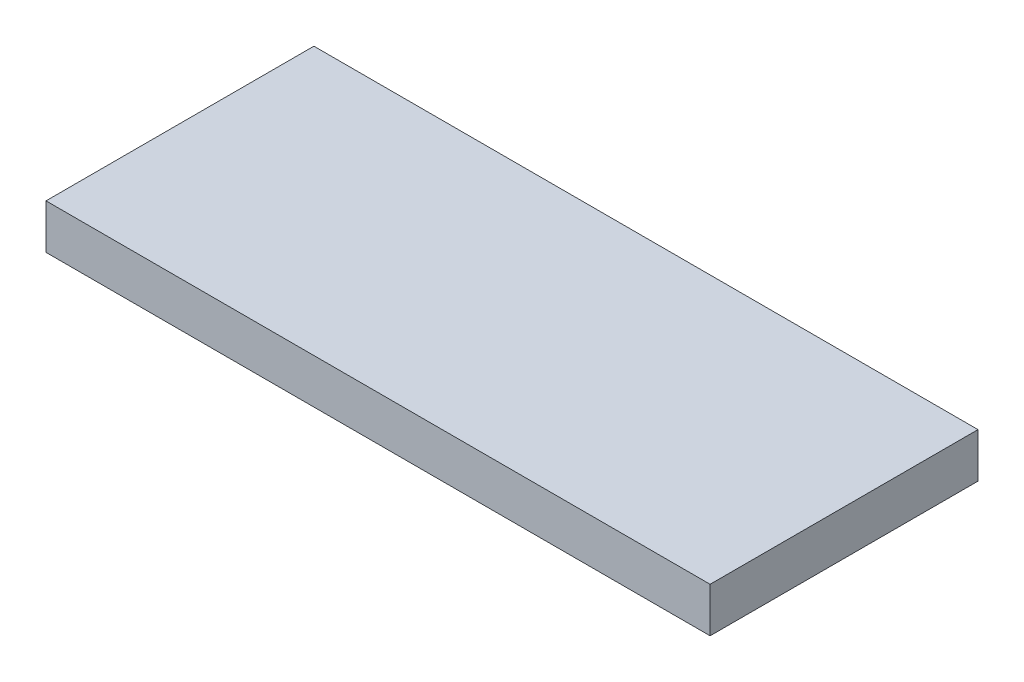
SolidWorks part; units mm, degrees
ref_plane "Front Plane" through (0, 0, 0) normal (0, 0, 1) x (1, 0, 0)
ref_plane "Top Plane" through (0, 0, 0) normal (0, 1, 0) x (1, 0, 0)
ref_plane "Right Plane" through (0, 0, 0) normal (1, 0, 0) x (0, 0, -1)
sketch "Sketch1" plane through (0, 0, 0) normal (0, 0, 1) x (1, 0, 0)
  line L0 (0, 0) -> (0, 76.2)
  line L5 (0, 76.2) -> (88.098, 76.2)
  line L6 (88.098, 76.2) -> (88.098, 101.6)
  line L7 (0, 0) -> (6.35, 0)
  line L8 (6.35, 0) -> (6.35, 76.2)
  line L9 (6.35, 76.2) -> (6.35, 69.85)
  line L10 (6.35, 69.85) -> (101.1141, 69.85)
  line L11 (88.098, 101.6) -> (94.448, 101.6)
  line L12 (94.448, 101.6) -> (94.448, 69.85)
  dimension "D1" = 25.4
  dimension "D2" = 76.2
extrude "Boss-Extrude1" add sketch "Sketch1" along normal blind 38.1 contours L7 L8 L5 L0 | L12 L11 L6 L5 L8 L10 region at (3.175, 38.1, 0) region at (47.224, 75.2636, 0)
sketch "Sketch2" plane through (0, 0, 0) normal (-1, 0, 0) x (0, 0, 1)
  line L0 (19.05, 20.32) -> (19.05, 42.672)
  line L1 (0, 0) -> (0, 76.2) construction
  line L2 (38.1, 0) -> (0, 0)
  line L3 (38.1, 0) -> (38.1, 50.8)
  line L4 (38.1, 50.8) -> (0, 50.8)
  line L5 (0, 0) -> (0, 50.8)
  line L6 (38.1, 0) -> (38.1, 20.32)
  line L7 (38.1, 20.32) -> (0, 20.32)
  circle A0 centre (19.05, 20.32) radius 11.049
  circle A1 centre (19.05, 42.672) radius 3.556
  point P13 (19.05, 20.32)
  dimension "D1" = 22.352
  dimension "D2" = 20.32
extrude "Cut-Extrude1" cut sketch "Sketch2" against normal blind 6.35 contours A0
extrude "Cut-Extrude2" cut sketch "Sketch2<4>" against normal blind 6.35 contours A1
sketch "Sketch2<4>" plane through (0, 0, 0) normal (-1, 0, 0) x (0, 0, 1) same geometry as "Sketch2"
sketch "Sketch4" plane through (0, 0, 38.1) normal (0, 0, 1) x (1, 0, 0)
  line L5 (88.098, 76.2) -> (102.3424, 76.2)
  line L6 (88.098, 76.2) -> (88.098, 112.6724)
  line L7 (88.098, 112.6724) -> (102.3424, 112.6724)
  line L8 (102.3424, 76.2) -> (102.3424, 112.6724)
  line L9 (6.35, 69.85) -> (-28.4909, 69.85)
  line L10 (6.35, 69.85) -> (6.35, -10.2972)
  line L11 (6.35, -10.2972) -> (-28.4909, -10.2972)
  line L12 (-28.4909, 69.85) -> (-28.4909, -10.2972)
extrude "Cut-Extrude4" cut sketch "Sketch4" against normal blind 76.2
